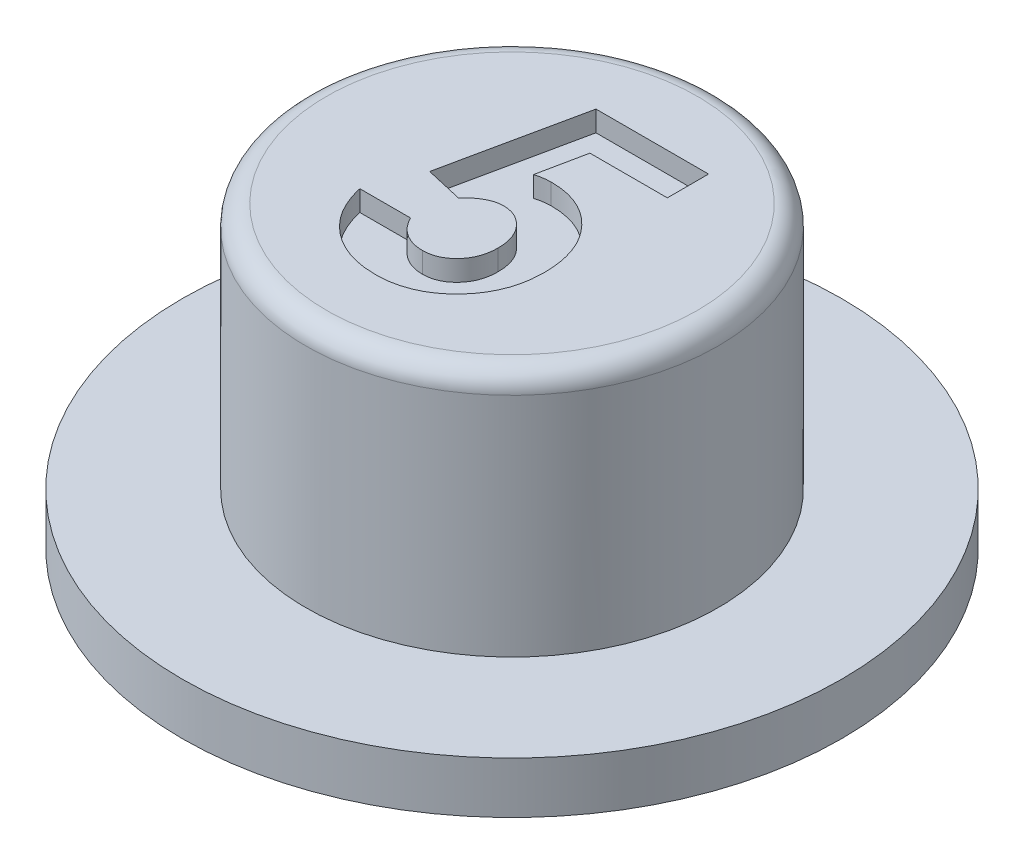
SolidWorks part; units mm, degrees
ref_plane "Front Plane" through (0, 0, 0) normal (0, 0, 1) x (1, 0, 0)
ref_plane "Top Plane" through (0, 0, 0) normal (0, 1, 0) x (1, 0, 0)
ref_plane "Right Plane" through (0, 0, 0) normal (1, 0, 0) x (0, 0, -1)
sketch "Sketch1" plane through (0, 0, 0) normal (0, 0, 1) x (1, 0, 0)
  line L1 (0, 7.25) -> (5, 7.25)
  line L2 (5, 7.25) -> (5, 1.25)
  line L3 (5, 1.25) -> (8, 1.25)
  line L4 (8, 1.25) -> (8, 0)
  line L6 (0, 7.25) -> (0, 6.9292) construction
  line L7 (0, 7.25) -> (0, 0)
  line L10 (0, 0) -> (8, 0)
  dimension "D1" = 5
  dimension "D2" = 3
  dimension "D3" = 6
  dimension "D4" = 1.25
revolve "Revolve1" add sketch "Sketch1" angle 360 about L6
sketch "Sketch2" plane through (0, 0, 0) normal (0, -1, 0) x (1, 0, 0)
  line L1 (-1.75, -1.25) -> (1.75, -1.25)
  line L2 (-1.75, -1.25) -> (-1.75, 1.25)
  line L3 (-1.75, 1.25) -> (1.75, 1.25)
  line L4 (1.75, -1.25) -> (1.75, 1.25)
  line L5 (-1.75, -1.25) -> (1.75, 1.25) construction
  line L6 (-1.75, 1.25) -> (1.75, -1.25) construction
  point P0 (0, 0)
  dimension "D1" = 3.5
  dimension "D2" = 2.5
extrude "Cut-Extrude1" cut sketch "Sketch2" against normal blind 3.5 contours L3 L4 L1 L2
fillet "Fillet1" radius 0.5 1 edges at (-5, 7.25, 0)
sketch "Sketch3" plane through (0, 7.25, 0) normal (0, 1, 0) x (1, 0, 0)
  line L0 (-3.3541, -3) -> (3.3541, -3) construction
  line L1 (0, 0) -> (0, -3) construction
  circle A0 centre (0, 0) radius 4.5 construction
  text T0 "5" font "Century Gothic" height 6
  dimension "D1" = 3
extrude "Cut-Extrude2" cut sketch "Sketch3" against normal blind 0.5
